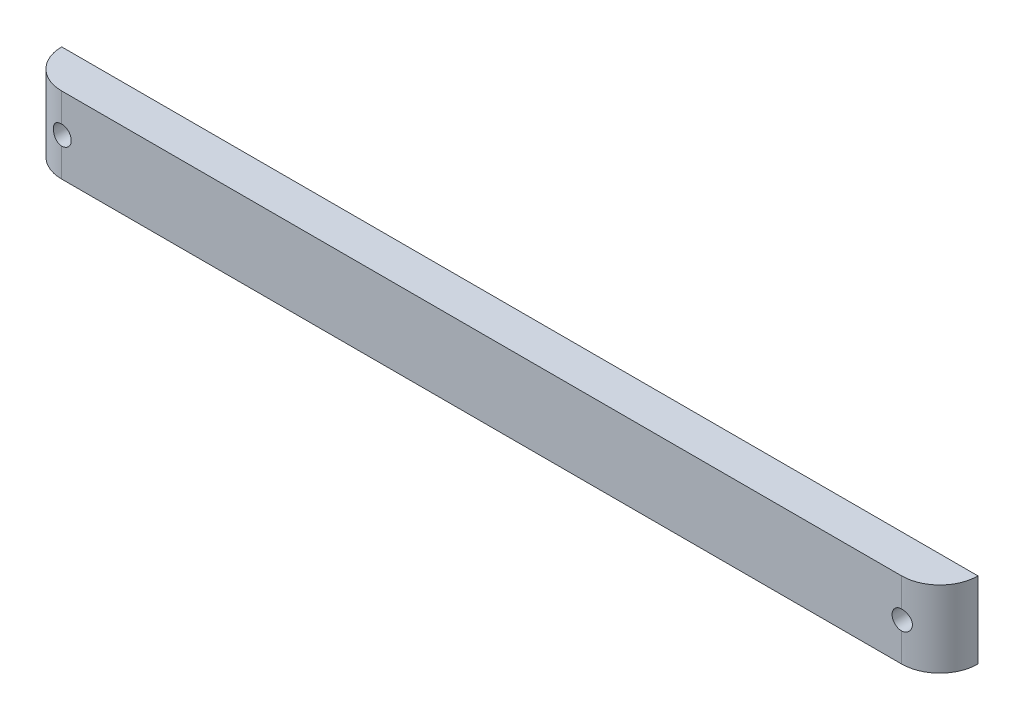
SolidWorks part; units mm, degrees
ref_plane "Front Plane" through (0, 0, 0) normal (0, 0, 1) x (1, 0, 0)
ref_plane "Top Plane" through (0, 0, 0) normal (0, 1, 0) x (1, 0, 0)
ref_plane "Right Plane" through (0, 0, 0) normal (1, 0, 0) x (0, 0, -1)
sketch "Sketch1" plane through (0, 0, 0) normal (0, 0, 1) x (1, 0, 0)
  line L1 (0, 0) -> (240, 0)
  line L2 (0, 0) -> (0, 20)
  line L3 (0, 20) -> (240, 20)
  line L4 (240, 0) -> (240, 20)
  circle A0 centre (230, 10) radius 2.5
  circle A1 centre (10, 10) radius 2.5
  point P9 (0, 10)
  dimension "D3" = 5
  dimension "D1" = 240
  dimension "D2" = 20
  dimension "D4" = 10
  dimension "D5" = 10
  dimension "D6" = 10
  dimension "D7" = 10
extrude "Boss-Extrude1" add sketch "Sketch1" along normal blind 10
fillet "Fillet1" radius 10 2 edges at (240, 10, 10) (0, 10, 10)
